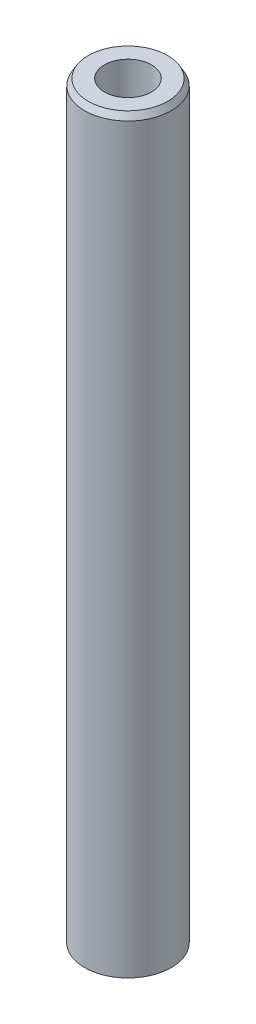
SolidWorks part; units mm, degrees
ref_plane "Front Plane" through (0, 0, 0) normal (0, 0, 1) x (1, 0, 0)
ref_plane "Top Plane" through (0, 0, 0) normal (0, 1, 0) x (1, 0, 0)
ref_plane "Right Plane" through (0, 0, 0) normal (1, 0, 0) x (0, 0, -1)
sketch "Sketch1" plane through (0, 0, 0) normal (0, 1, 0) x (1, 0, 0)
  circle A0 centre (0, 0) radius 15
  dimension "SHAFT_OD" = 30
extrude "Boss-Extrude1" add sketch "Sketch1" along normal blind 260.3028
sketch "Sketch2" plane through (0, 0, 0) normal (0, 1, 0) x (1, 0, 0)
  circle A0 centre (0, 0) radius 8.1556
  dimension "BORE_D" = 16.3112
extrude "Cut-Extrude1" cut sketch "Sketch2" along normal through all
chamfer "Chamfer1" distance 2.1805 angle 30 2 edges at (0, 260.3028, 15) (0, 0, 15) first distance on face at (0, 260.3028, 15) first distance on face at (0, 0, 8.1556)
